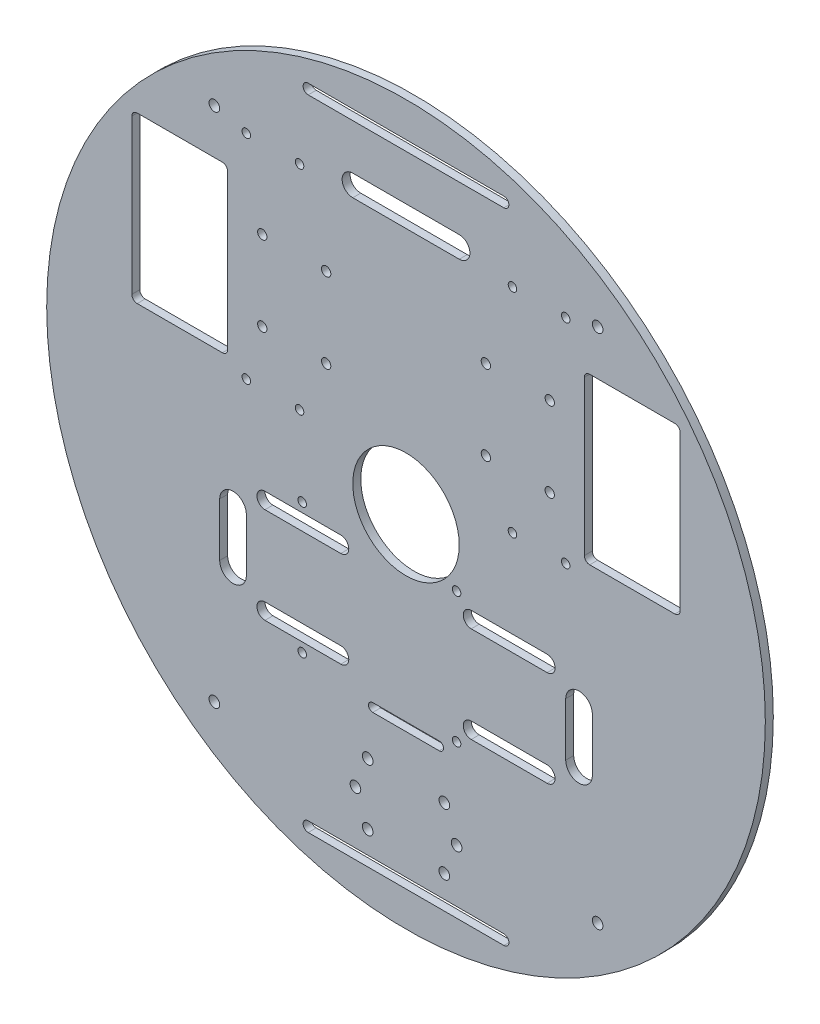
SolidWorks part; units mm, degrees
ref_plane "前视基准面" through (0, 0, 0) normal (0, 0, 1) x (1, 0, 0)
ref_plane "上视基准面" through (0, 0, 0) normal (0, 1, 0) x (1, 0, 0)
ref_plane "右视基准面" through (0, 0, 0) normal (1, 0, 0) x (0, 0, -1)
sketch "草图1" plane through (0, 0, 0) normal (0, 0, 1) x (1, 0, 0)
  line L0 (0, 135) -> (0, -135) construction
  line L1 (0, -98.1495) -> (85, 49.0748) construction
  line L2 (85, 49.0748) -> (-85, 49.0748) construction
  line L3 (-85, 49.0748) -> (0, -98.1495) construction
  line L4 (-103, 80.0748) -> (-67, 80.0748)
  line L5 (-103, 80.0748) -> (-103, 18.0748)
  line L6 (-103, 18.0748) -> (-67, 18.0748)
  line L7 (-67, 80.0748) -> (-67, 18.0748)
  line L8 (-103, 80.0748) -> (-67, 18.0748) construction
  line L9 (-103, 18.0748) -> (-67, 80.0748) construction
  line L10 (103, 80.0748) -> (67, 80.0748)
  line L11 (67, 80.0748) -> (67, 18.0748)
  line L12 (103, 80.0748) -> (67, 18.0748) construction
  line L13 (103, 18.0748) -> (67, 18.0748)
  line L14 (103, 18.0748) -> (67, 80.0748) construction
  line L15 (103, 80.0748) -> (103, 18.0748)
  line L17 (-14.4, -86.6495) -> (14.4, -86.6495) construction
  line L18 (-14.4, -86.6495) -> (-14.4, -109.6495) construction
  line L19 (-14.4, -109.6495) -> (14.4, -109.6495) construction
  line L20 (14.4, -86.6495) -> (14.4, -109.6495) construction
  line L21 (-14.4, -86.6495) -> (14.4, -109.6495) construction
  line L22 (-14.4, -109.6495) -> (14.4, -86.6495) construction
  line L29 (-54, 64.0748) -> (-30, 64.0748) construction
  line L30 (-54, 64.0748) -> (-54, 34.0748) construction
  line L31 (-54, 34.0748) -> (-30, 34.0748) construction
  line L32 (-30, 64.0748) -> (-30, 34.0748) construction
  line L33 (-54, 64.0748) -> (-30, 34.0748) construction
  line L34 (-54, 34.0748) -> (-30, 64.0748) construction
  circle A0 centre (0, 0) radius 135
  circle A1 centre (0, 0) radius 49.0748 construction
  circle A2 centre (-54, 64.0748) radius 1.75
  circle A3 centre (-30, 64.0748) radius 1.75
  circle A4 centre (-54, 34.0748) radius 1.75
  circle A5 centre (-30, 34.0748) radius 1.75
  circle A6 centre (54, 34.0748) radius 1.75
  circle A7 centre (30, 34.0748) radius 1.75
  circle A8 centre (30, 64.0748) radius 1.75
  circle A9 centre (54, 64.0748) radius 1.75
  circle A10 centre (19, -98.1495) radius 2
  circle A11 centre (14.4, -86.6495) radius 2
  circle A12 centre (14.4, -109.6495) radius 2
  circle A13 centre (-14.4, -86.6495) radius 2
  circle A14 centre (-14.4, -109.6495) radius 2
  circle A15 centre (-19, -98.1495) radius 2
  point P25 (0, 49.0748)
  point P26 (-42, 49.0748)
  point P30 (0, 49.0748)
  dimension "D1" = 270
  dimension "D9" = 3.5
  dimension "D10" = 3.5
  dimension "D11" = 3.5
  dimension "D12" = 3.5
  dimension "D14" = 19
  dimension "D2" = 36
  dimension "D3" = 62
  dimension "D4" = 170
  dimension "D5" = 13
  dimension "D6" = 28.8
  dimension "D7" = 24
  dimension "D8" = 30
  dimension "D13" = 23
  dimension "D15" = 60
extrude "凸台-拉伸1" add sketch "草图1" along normal blind 3 contours A0 A14 A9 A7 L10 L15 L13 L11 A2 A3 A4 A5 A6 A8 A10 A11 A12 A13 A15 region at (0, -4.0929, 0)
fillet "圆角1" radius 2 8 edges at (103, 80.0748, 1.5) (67, 80.0748, 1.5) (67, 18.0748, 1.5) (103, 18.0748, 1.5) (-67, 18.0748, 1.5) (-103, 18.0748, 1.5) (-103, 80.0748, 1.5) (-67, 80.0748, 1.5)
sketch "草图2" plane through (0, 0, 3) normal (0, 0, 1) x (1, 0, 0)
  line L0 (0, 97) -> (0, -98.1495) construction
  line L1 (-72, 97) -> (72, 97) construction
  line L2 (-72, 97) -> (-72, -97) construction
  line L3 (-72, -97) -> (72, -97) construction
  line L4 (72, 97) -> (72, -97) construction
  line L5 (-72, 97) -> (72, -97) construction
  line L6 (-72, -97) -> (72, 97) construction
  line L7 (24.5056, -55) -> (53, -55)
  line L8 (-53, -19) -> (-24.5056, -19)
  line L9 (-53, -19) -> (-53, -61) construction
  line L10 (-53, -61) -> (-24.5056, -61)
  line L11 (53, -19) -> (53, -61) construction
  line L12 (-53, -19) -> (53, -61) construction
  line L13 (-53, -61) -> (53, -19) construction
  line L14 (-53, -25) -> (-24.5056, -25)
  line L15 (-53, -25) -> (-53, -55) construction
  line L16 (-53, -55) -> (-24.5056, -55)
  line L17 (53, -25) -> (53, -55) construction
  line L18 (-53, -25) -> (53, -55) construction
  line L19 (-53, -55) -> (53, -25) construction
  line L20 (24.5056, -25) -> (53, -25)
  line L21 (24.5056, -19) -> (53, -19)
  line L22 (24.5056, -61) -> (53, -61)
  line L23 (40, 94) -> (40, 14) construction
  line L24 (-65, -30) -> (65, -30) construction
  line L25 (-65, -30) -> (-65, -50) construction
  line L26 (-65, -50) -> (65, -50) construction
  line L27 (65, -30) -> (65, -50) construction
  line L28 (-65, -30) -> (65, -50) construction
  line L29 (-65, -50) -> (65, -30) construction
  line L30 (-70, -30) -> (-60, -30) construction
  line L31 (-70, -30) -> (-70, -50)
  line L32 (-70, -50) -> (-60, -50) construction
  line L33 (-60, -30) -> (-60, -50)
  line L34 (-70, -30) -> (-60, -50) construction
  line L35 (-70, -50) -> (-60, -30) construction
  line L36 (60, -30) -> (70, -30) construction
  line L37 (60, -30) -> (60, -50)
  line L38 (60, -50) -> (70, -50) construction
  line L39 (70, -30) -> (70, -50)
  line L40 (60, -30) -> (70, -50) construction
  line L41 (60, -50) -> (70, -30) construction
  line L43 (35, -12.5) -> (-35, -12.5) construction
  line L44 (35, -12.5) -> (35, -67.5) construction
  line L45 (-42.5, -12) -> (42.5, -12) construction
  line L46 (-42.5, -12) -> (-42.5, -68) construction
  line L47 (-42.5, -68) -> (42.5, -68) construction
  line L48 (-135, 0) -> (135, 0) construction
  line L49 (-36.7556, -118.1) -> (36.7556, -121.9) construction
  line L50 (-36.7556, 121.9) -> (36.7556, 121.9)
  line L51 (-36.7556, 121.9) -> (-36.7556, 118.1) construction
  line L52 (-36.7556, 118.1) -> (36.7556, 118.1)
  line L53 (36.7556, 121.9) -> (36.7556, 118.1) construction
  line L54 (-36.7556, 121.9) -> (36.7556, 118.1) construction
  line L55 (-36.7556, 118.1) -> (36.7556, 121.9) construction
  line L56 (-36.7556, -121.9) -> (36.7556, -118.1) construction
  line L57 (36.7556, -121.9) -> (36.7556, -118.1) construction
  line L58 (-36.7556, -121.9) -> (-36.7556, -118.1) construction
  line L59 (-36.7556, -118.1) -> (36.7556, -118.1)
  line L60 (-36.7556, -121.9) -> (36.7556, -121.9)
  line L61 (-40, 94) -> (-40, 14) construction
  line L62 (-60, 94) -> (60, 94) construction
  line L63 (-60, 94) -> (-60, 14) construction
  line L64 (-60, 14) -> (60, 14) construction
  line L65 (60, 94) -> (60, 14) construction
  line L66 (-60, 94) -> (60, 14) construction
  line L67 (-60, 14) -> (60, 94) construction
  line L68 (42.5, -12) -> (42.5, -68) construction
  line L69 (-42.5, -12) -> (42.5, -68) construction
  line L70 (-42.5, -68) -> (42.5, -12) construction
  line L71 (-39, -15.5) -> (19, -15.5) construction
  line L72 (-39, -15.5) -> (-39, -64.5) construction
  line L73 (-39, -64.5) -> (19, -64.5) construction
  line L74 (19, -15.5) -> (19, -64.5) construction
  line L75 (-39, -15.5) -> (19, -64.5) construction
  line L76 (-39, -64.5) -> (19, -15.5) construction
  line L77 (35, -67.5) -> (-35, -67.5) construction
  line L78 (-35, -12.5) -> (-35, -67.5) construction
  line L79 (35, -12.5) -> (-35, -67.5) construction
  line L80 (35, -67.5) -> (-35, -12.5) construction
  line L81 (12.5, -70.7) -> (-12.5, -70.7)
  line L82 (12.5, -70.7) -> (12.5, -67.5) construction
  line L83 (12.5, -67.5) -> (-12.5, -67.5)
  line L84 (-12.5, -70.7) -> (-12.5, -67.5) construction
  line L85 (12.5, -70.7) -> (-12.5, -67.5) construction
  line L86 (12.5, -67.5) -> (-12.5, -70.7) construction
  line L87 (20, 101) -> (-20, 101)
  line L88 (20, 101) -> (20, 93) construction
  line L89 (20, 93) -> (-20, 93)
  line L90 (-20, 101) -> (-20, 93) construction
  line L91 (20, 101) -> (-20, 93) construction
  line L92 (20, 93) -> (-20, 101) construction
  circle A0 centre (0, 0) radius 20
  circle A1 centre (-72, 97) radius 2
  circle A2 centre (72, 97) radius 2
  circle A3 centre (72, -97) radius 2
  circle A4 centre (-72, -97) radius 2
  arc A5 (-53, -19) -> (-53, -25) centre (-53, -22) ccw
  arc A6 (-53, -55) -> (-53, -61) centre (-53, -58) ccw
  arc A7 (-24.5056, -19) -> (-24.5056, -25) centre (-24.5056, -22) cw
  arc A8 (-24.5056, -61) -> (-24.5056, -55) centre (-24.5056, -58) ccw
  arc A9 (53, -55) -> (53, -61) centre (53, -58) cw
  arc A10 (53, -19) -> (53, -25) centre (53, -22) cw
  arc A11 (24.5056, -61) -> (24.5056, -55) centre (24.5056, -58) cw
  arc A12 (24.5056, -19) -> (24.5056, -25) centre (24.5056, -22) ccw
  arc A13 (-70, -30) -> (-60, -30) centre (-65, -30) cw
  arc A14 (-70, -50) -> (-60, -50) centre (-65, -50) ccw
  arc A15 (60, -30) -> (70, -30) centre (65, -30) cw
  arc A16 (60, -50) -> (70, -50) centre (65, -50) ccw
  circle A17 centre (-60, 94) radius 1.6
  circle A18 centre (-60, 14) radius 1.6
  circle A19 centre (-40, 94) radius 1.6
  circle A20 centre (-40, 14) radius 1.6
  circle A21 centre (60, 14) radius 1.6
  circle A22 centre (60, 94) radius 1.6
  circle A23 centre (40, 94) radius 1.6
  circle A24 centre (40, 14) radius 1.6
  circle A25 centre (0, 0) radius 135 construction
  arc A26 (36.7556, 121.9) -> (36.7556, 118.1) centre (36.7556, 120) cw
  arc A27 (-36.7556, 121.9) -> (-36.7556, 118.1) centre (-36.7556, 120) ccw
  arc A28 (-36.7556, -121.9) -> (-36.7556, -118.1) centre (-36.7556, -120) cw
  arc A29 (36.7556, -121.9) -> (36.7556, -118.1) centre (36.7556, -120) ccw
  circle A30 centre (-39, -15.5) radius 1.6
  circle A31 centre (19, -15.5) radius 1.6
  circle A32 centre (-39, -64.5) radius 1.6
  circle A33 centre (19, -64.5) radius 1.6
  arc A34 (-12.5, -67.5) -> (-12.5, -70.7) centre (-12.5, -69.1) ccw
  arc A35 (12.5, -67.5) -> (12.5, -70.7) centre (12.5, -69.1) cw
  arc A36 (20, 101) -> (20, 93) centre (20, 97) cw
  arc A37 (-20, 101) -> (-20, 93) centre (-20, 97) ccw
  point P25 (0, 54)
  point P32 (0, -40)
  point P37 (-65, -40)
  point P38 (0, -40)
  point P39 (0, -40)
  point P52 (65, -40)
  point P61 (0, -40)
  point P77 (-10, -40)
  point P83 (0, 120)
  point P96 (0, -120)
  point P97 (0, -40)
  point P106 (-42.5, -40)
  point P111 (0, -40)
  point P116 (0, -69.1)
  dimension "D1" = 144
  dimension "D13" = 3.8
  dimension "D15" = 4
  dimension "D16" = 4
  dimension "D17" = 4
  dimension "D18" = 4
  dimension "D12" = 56
  dimension "D26" = 6
  dimension "D27" = 3
  dimension "D28" = 3
  dimension "D2" = 194
  dimension "D3" = 30
  dimension "D4" = 20
  dimension "D5" = 106
  dimension "D6" = 130
  dimension "D7" = 40
  dimension "D8" = 10
  dimension "D9" = 10
  dimension "D10" = 54
  dimension "D11" = 40
  dimension "D14" = 120
  dimension "D19" = 80
  dimension "D20" = 120
  dimension "D21" = 85
  dimension "D22" = 3.5
  dimension "D23" = 58
  dimension "D24" = 49
  dimension "D25" = 3.5
  dimension "D29" = 70
  dimension "D30" = 55
  dimension "D31" = 25
  dimension "D32" = 3.2
  dimension "D33" = 8
  dimension "D34" = 40
extrude "切除-拉伸1" cut sketch "草图2" against normal blind 10
sketch "草图3" plane through (0, 0, 3) normal (0, 0, 1) x (1, 0, 0)
  line L0 (0, 0) -> (0, -135) construction
  line L1 (0, 93) -> (0, 0) construction
  line L2 (35, -8.8786) -> (-35, -8.8786) construction
  line L3 (35, -8.8786) -> (35, -63.8786) construction
  line L4 (35, -63.8786) -> (-35, -63.8786) construction
  line L5 (-35, -8.8786) -> (-35, -63.8786) construction
  line L6 (35, -8.8786) -> (-35, -63.8786) construction
  line L7 (35, -63.8786) -> (-35, -8.8786) construction
  line L8 (-20, 93) -> (20, 93) construction
  circle A0 centre (0, 0) radius 135 construction
  point P6 (0, -36.3786)
  dimension "D1" = 55
  dimension "D2" = 70
  dimension "D3" = 93
